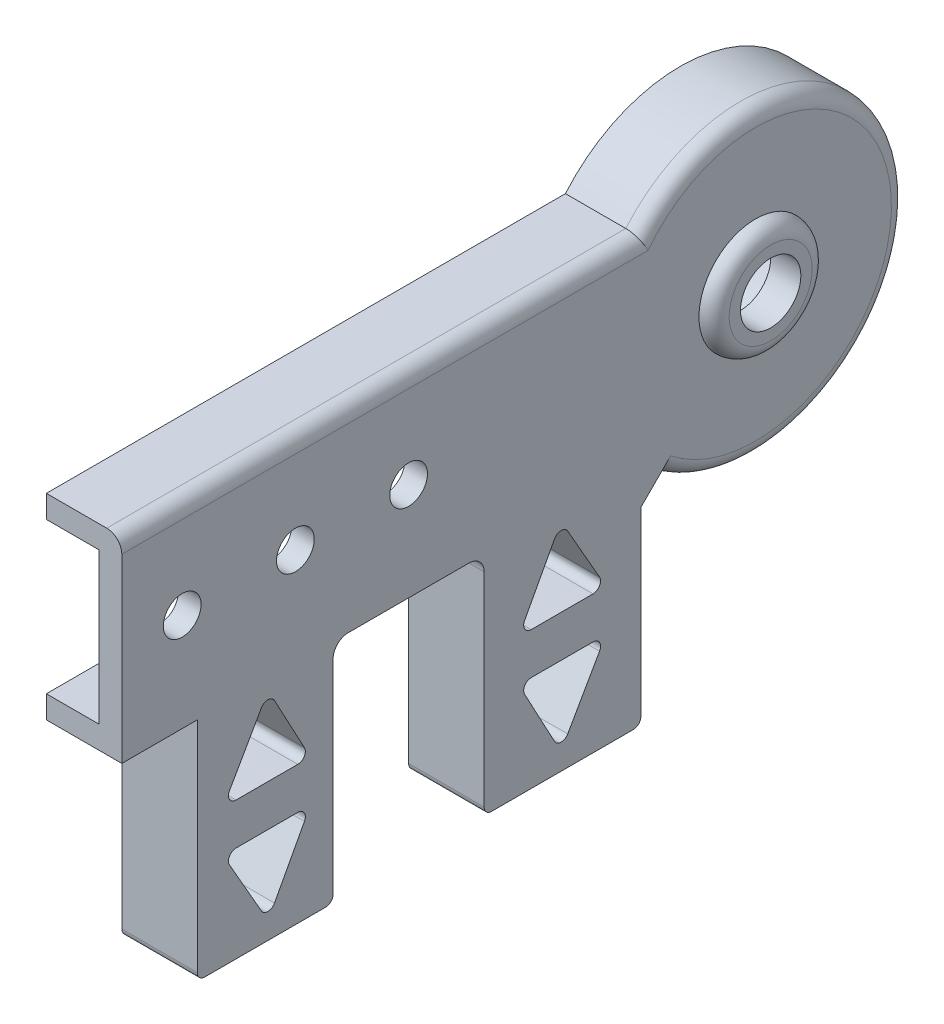
SolidWorks part; units mm, degrees
ref_plane "前视基准面" through (0, 0, 0) normal (0, 0, 1) x (1, 0, 0)
ref_plane "上视基准面" through (0, 0, 0) normal (0, 1, 0) x (1, 0, 0)
ref_plane "右视基准面" through (0, 0, 0) normal (1, 0, 0) x (0, 0, -1)
sketch "草图1" plane through (0, 0, 0) normal (1, 0, 0) x (0, 0, -1)
  line L1 (-31.9868, 13) -> (31.9868, 13)
  line L2 (-31.9868, 13) -> (-31.9868, -13)
  line L3 (-31.9868, -13) -> (31.9868, -13)
  line L4 (31.9868, 13) -> (31.9868, -13)
  line L5 (-31.9868, 13) -> (31.9868, -13) construction
  line L6 (-31.9868, -13) -> (31.9868, 13) construction
  circle A0 centre (31.9868, 0) radius 20
  point P0 (0, 0)
  dimension "D2" = 40
  dimension "D1" = 26
extrude "凸台-拉伸1" add sketch "草图1" along normal blind 10 contours L3 A0 L1 L4 | L1 L4 L3 L2 region at (0, 0, -37.7439)
sketch "草图2" plane through (10, 0, 0) normal (1, 0, 0) x (0, 0, -1)
  line L0 (-31.9868, 13) -> (-31.9868, -13) construction
  line L1 (-31.9868, 10) -> (13.0132, 10)
  line L2 (-31.9868, 10) -> (-31.9868, -10)
  line L3 (-31.9868, -10) -> (13.0132, -10)
  line L4 (13.0132, 10) -> (13.0132, -10)
  line L5 (-31.9868, 13) -> (16.7881, 13) construction
  line L6 (-31.9868, -13) -> (16.7881, -13) construction
  dimension "D1" = 3
  dimension "D2" = 3
  dimension "D3" = 45
extrude "切除-拉伸1" cut sketch "草图2" against normal blind 7
sketch "草图3" plane through (10, 0, 0) normal (1, 0, 0) x (0, 0, -1)
  circle A0 centre (31.9868, 0) radius 10
  dimension "D1" = 20
extrude "切除-拉伸2" cut sketch "草图3" against normal blind 8
sketch "草图4" plane through (2, 0, 0) normal (1, 0, 0) x (0, 0, -1)
  circle A0 centre (31.9868, 0) radius 4
  dimension "D1" = 8
extrude "切除-拉伸3" cut sketch "草图4" against normal blind 7
sketch "草图6" plane through (0, -13, 0) normal (0, -1, 0) x (1, 0, 0)
  line L0 (10, 31.9868) -> (10, -16.7881) construction
  line L1 (0, -16.7881) -> (10, -16.7881)
  line L2 (0, -16.7881) -> (0, -8.7881)
  line L3 (0, -8.7881) -> (10, -8.7881)
  line L4 (10, -16.7881) -> (10, -8.7881)
  line L6 (0, 31.9868) -> (10, 31.9868)
  line L7 (0, 31.9868) -> (0, 23.9868)
  line L8 (0, 23.9868) -> (10, 23.9868)
  line L9 (10, 31.9868) -> (10, 23.9868)
  dimension "D1" = 8
  dimension "D2" = 8
extrude "凸台-拉伸2" add sketch "草图6" along normal blind 15
chamfer "倒角2" distance 5 angle 45 1 edges at (5, -13, -16.7881) first distance on face at (5, -20.5, -16.7881)
sketch "草图7" plane through (0, 0, 31.9868) normal (0, 0, 1) x (1, 0, 0)
  line L8 (3, -10) -> (3, 10)
  line L9 (3, 10) -> (10, 10)
  line L10 (10, 10) -> (10, 13)
  line L11 (10, 13) -> (0, 13)
  line L12 (0, 13) -> (0, -28)
  line L13 (0, -28) -> (10, -28)
  line L14 (10, -28) -> (10, -10)
  line L15 (10, -10) -> (3, -10)
  line L16 (3, -10) -> (3, 10)
  line L17 (3, 10) -> (10, 10)
  line L18 (10, 10) -> (10, 13)
  line L19 (10, 13) -> (0, 13)
  line L20 (0, 13) -> (0, -28)
  line L21 (0, -28) -> (10, -28)
  line L22 (10, -28) -> (10, -10)
  line L23 (10, -10) -> (3, -10)
  dimension "D1" = 0
extrude "凸台-拉伸3" add sketch "草图7" along normal blind 20
sketch "草图8" plane through (0, -13, 0) normal (0, -1, 0) x (1, 0, 0)
  line L0 (10, 23.9868) -> (10, -8.7881) construction
  line L1 (0, -8.7881) -> (10, -8.7881)
  line L2 (0, -8.7881) -> (0, 3.9868)
  line L3 (0, 3.9868) -> (10, 3.9868)
  line L4 (10, -8.7881) -> (10, 3.9868)
  line L5 (0, 23.9868) -> (10, 23.9868) construction
  dimension "D1" = 20
extrude "凸台-拉伸4" add sketch "草图8" along normal up to surface (15 mm away) up to face at (5, -28, -12.7881)
sketch "草图9" plane through (0, 0, -13.0132) normal (0, 0, 1) x (1, 0, 0)
  line L4 (10, -10) -> (10, 10)
  line L5 (10, 10) -> (3, 10)
  line L6 (3, 10) -> (3, -10)
  line L7 (3, -10) -> (10, -10)
  line L8 (10, -10) -> (10, 10)
  line L9 (10, 10) -> (3, 10)
  line L10 (3, 10) -> (3, -10)
  line L11 (3, -10) -> (10, -10)
  dimension "D1" = 0
extrude "凸台-拉伸5" add sketch "草图9" along normal blind 10
sketch "草图10" plane through (0, 0, -3.0132) normal (0, 0, 1) x (1, 0, 0)
  line L4 (3, -10) -> (10, -10)
  line L5 (10, -10) -> (10, 10)
  line L6 (10, 10) -> (3, 10)
  line L7 (3, 10) -> (3, -10)
  line L8 (3, -10) -> (10, -10)
  line L9 (10, -10) -> (10, 10)
  line L10 (10, 10) -> (3, 10)
  line L11 (3, 10) -> (3, -10)
  dimension "D1" = 0
extrude "凸台-拉伸6" add sketch "草图10" along normal blind 7
sketch "草图11" plane through (10, 0, 0) normal (1, 0, 0) x (0, 0, -1)
  line L0 (-51.9868, -28) -> (-51.9868, -10) construction
  line L1 (-51.9868, -13) -> (-41.9868, -13)
  line L2 (-51.9868, -13) -> (-51.9868, -28)
  line L3 (-51.9868, -28) -> (-41.9868, -28)
  line L4 (-41.9868, -13) -> (-41.9868, -28)
  line L5 (-23.9868, -28) -> (-51.9868, -28) construction
  dimension "D1" = 10
extrude "切除-拉伸5" cut sketch "草图11" against normal through all
sketch "草图12" plane through (10, 0, 0) normal (1, 0, 0) x (0, 0, -1)
  line L4 (-3.9868, -10) -> (-3.9868, 10)
  line L5 (-3.9868, 10) -> (-51.9868, 10)
  line L6 (-51.9868, 10) -> (-51.9868, -10)
  line L7 (-51.9868, -10) -> (-3.9868, -10)
  line L8 (-3.9868, -10) -> (-3.9868, 10)
  line L9 (-3.9868, 10) -> (-51.9868, 10)
  line L10 (-51.9868, 10) -> (-51.9868, -10)
  line L11 (-51.9868, -10) -> (-3.9868, -10)
  circle A1 centre (31.9868, 0) radius 10
  circle A2 centre (31.9868, 0) radius 10
  dimension "D1" = 0
  dimension "D2" = 0
extrude "凸台-拉伸7" add sketch "草图12" against normal blind 10
sketch "草图13" plane through (0, 0, 0) normal (-1, 0, 0) x (0, 0, 1)
  circle A0 centre (-31.9868, 0) radius 10
  dimension "D1" = 20
extrude "切除-拉伸6" cut sketch "草图13" against normal blind 8
sketch "草图14" plane through (8, 0, 0) normal (-1, 0, 0) x (0, 0, 1)
  circle A0 centre (-31.9868, 0) radius 4
  dimension "D1" = 8
extrude "切除-拉伸7" cut sketch "草图14" against normal blind 8
sketch "草图15" plane through (0, 0, 0) normal (-1, 0, 0) x (0, 0, 1)
  line L0 (51.9868, 13) -> (51.9868, -13) construction
  line L1 (3.9868, 10) -> (51.9868, 10)
  line L2 (3.9868, 10) -> (3.9868, -10)
  line L3 (3.9868, -10) -> (51.9868, -10)
  line L4 (51.9868, 10) -> (51.9868, -10)
  line L5 (41.9868, -13) -> (51.9868, -13) construction
  line L6 (51.9868, 13) -> (-16.7881, 13) construction
  point P8 (46.9868, -13)
  dimension "D1" = 3
  dimension "D2" = 3
  dimension "D3" = 48
extrude "切除-拉伸8" cut sketch "草图15" against normal blind 7
sketch "草图16" plane through (0, -28, 0) normal (0, -1, 0) x (1, 0, 0)
  line L4 (10, 41.9868) -> (0, 41.9868)
  line L5 (0, 41.9868) -> (0, 23.9868)
  line L6 (0, 23.9868) -> (10, 23.9868)
  line L7 (10, 23.9868) -> (10, 41.9868)
  line L8 (10, 41.9868) -> (0, 41.9868)
  line L9 (0, 41.9868) -> (0, 23.9868)
  line L10 (0, 23.9868) -> (10, 23.9868)
  line L11 (10, 23.9868) -> (10, 41.9868)
  line L12 (0, 3.9868) -> (0, -16.7881)
  line L13 (0, -16.7881) -> (10, -16.7881)
  line L14 (10, -16.7881) -> (10, 3.9868)
  line L15 (10, 3.9868) -> (0, 3.9868)
  line L16 (0, 3.9868) -> (0, -16.7881)
  line L17 (0, -16.7881) -> (10, -16.7881)
  line L18 (10, -16.7881) -> (10, 3.9868)
  line L19 (10, 3.9868) -> (0, 3.9868)
  dimension "D1" = 0
  dimension "D2" = 0
extrude "凸台-拉伸8" add sketch "草图16" along normal blind 15
sketch "草图17" plane through (0, 0, 0) normal (-1, 0, 0) x (0, 0, 1)
  line L0 (-0.591, -30.2719) -> (-12.1701, -30.2719)
  line L1 (-12.1701, -30.2719) -> (-6.1999, -40.7198)
  line L2 (-6.1999, -40.7198) -> (-0.591, -30.2719)
  line L3 (-16.7881, -27.5164) -> (41.9868, -27.5164) construction
  line L4 (-16.7881, -43) -> (-16.7881, -18) construction
  line L5 (41.9868, -43) -> (41.9868, -13) construction
  line L6 (-6.1999, -14.3129) -> (-0.591, -24.7609)
  line L7 (-12.1701, -24.7609) -> (-6.1999, -14.3129)
  line L8 (-0.591, -24.7609) -> (-12.1701, -24.7609)
  line L9 (13.2035, -16.0351) -> (13.2035, -42.5568) construction
  line L10 (43.195, -27.5164) -> (-15.5798, -27.5164) construction
  line L11 (26.9979, -24.7609) -> (38.5771, -24.7609)
  line L12 (38.5771, -24.7609) -> (32.6068, -14.3129)
  line L13 (32.6068, -14.3129) -> (26.9979, -24.7609)
  line L14 (32.6068, -40.7198) -> (26.9979, -30.2719)
  line L15 (38.5771, -30.2719) -> (32.6068, -40.7198)
  line L16 (26.9979, -30.2719) -> (38.5771, -30.2719)
extrude "切除-拉伸9" cut sketch "草图17" against normal blind 15
fillet "圆角1" radius 1 16 edges at (5, -43, -16.7881) (5, -43, 3.9868) (5, -43, 41.9868) (5, -43, 23.9868) (5, -14.3129, 32.6068) (5, -24.7609, 38.5771) (5, -24.7609, 26.9979) (5, -30.2719, 26.9979) (5, -40.7198, 32.6068) (5, -30.2719, 38.5771) (5, -24.7609, -0.591) (5, -14.3129, -6.1999) (5, -24.7609, -12.1701) (5, -30.2719, -0.591) (5, -40.7198, -6.1999) (5, -30.2719, -12.1701)
fillet "圆角2" radius 2 4 edges at (10, 13, 17.5993) (10, 1.7679, -51.9085) (5, -13, 23.9868) (5, -13, 3.9868)
sketch "草图18" plane through (10, 0, 0) normal (1, 0, 0) x (0, 0, -1)
  circle A0 centre (31.9868, 0) radius 7.5
  circle A1 centre (31.9868, 0) radius 4 construction
  circle A2 centre (31.9868, 0) radius 4
  dimension "D1" = 15
extrude "凸台-拉伸9" add sketch "草图18" along normal blind 2
fillet "圆角3" radius 2 1 edges at (12, 0, -39.4868)
sketch "草图19" plane through (7, 0, 0) normal (-1, 0, 0) x (0, 0, 1)
  line L0 (0, 0) -> (71.4135, 0) construction
  line L2 (51.9868, -10) -> (51.9868, 10) construction
  circle A0 centre (43.9868, 0) radius 2.5
  circle A1 centre (28.9868, 0) radius 2.5
  circle A2 centre (13.9868, 0) radius 2.5
  dimension "D1" = 5
  dimension "D2" = 8
  dimension "D3" = 3
extrude "切除-拉伸10" cut sketch "草图19" against normal blind 3
